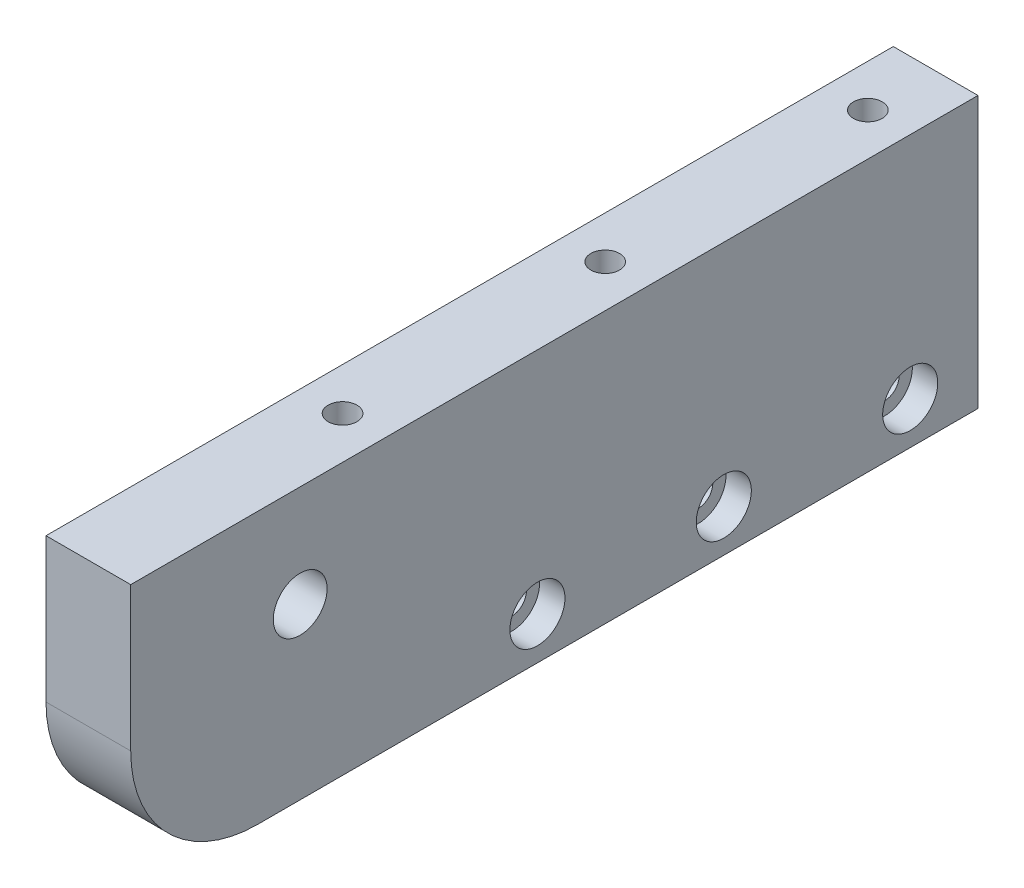
SolidWorks part; units mm, degrees
material "Plain Carbon Steel"
ref_plane "Front Plane" through (0, 0, 0) normal (0, 0, 1) x (1, 0, 0)
ref_plane "Top Plane" through (0, 0, 0) normal (0, 1, 0) x (1, 0, 0)
ref_plane "Right Plane" through (0, 0, 0) normal (1, 0, 0) x (0, 0, -1)
sketch "Sketch1" plane through (0, 0, 0) normal (1, 0, 0) x (0, 0, -1)
  line L1 (-50, -16) -> (50, -16)
  line L2 (-50, -16) -> (-50, 16)
  line L3 (-50, 16) -> (50, 16)
  line L4 (50, -16) -> (50, 16)
  line L5 (-50, -16) -> (50, 16) construction
  line L6 (-50, 16) -> (50, -16) construction
  circle A0 centre (-30, 4) radius 3.175
  point P0 (0, 0)
  dimension "D3" = 6.35
  dimension "D1" = 32
  dimension "D2" = 100
  dimension "D4" = 20
  dimension "D5" = 12
extrude "Boss-Extrude1" add sketch "Sketch1" along normal blind 10 contours L1 L4 L3 L2 A0 | A0 region at (0, -0.04, -0.2999)
fillet "Fillet1" radius 15 1 edges at (5, -16, 50)
hole_wizard "CBORE for M3 SHCS" positions "Sketch4" profile "Sketch5" counterbore size "M3" standard "ANSI Metric"
sketch "Sketch4" plane through (-726.2935, 26, -1323.2827) normal (0, 1, 0) x (1, 0, 0)
  line L3 (621.2935, -1281.2827) -> (621.2935, -1365.2827) construction
  line L5 (731.2935, -1281.2827) -> (731.2935, -1343.2827) construction
  circle A0 centre (731.2935, -1281.2827) radius 2.243
  circle A1 centre (731.2935, -1343.2827) radius 2.2384
  circle A3 centre (621.2935, -1281.2827) radius 2.3325
  circle A4 centre (621.2935, -1365.2827) radius 1.7576
  circle A5 centre (621.2935, -1323.2827) radius 1.8624
  circle A6 centre (731.2935, -1312.2827) radius 2.0271
  point P1 (731.2935, -1281.2827)
  point P8 (731.2935, -1343.2827)
  point P15 (621.2935, -1281.2827)
  point P17 (621.2935, -1365.2827)
  point P19 (621.2935, -1323.2827)
  point P27 (731.2935, -1312.2827)
sketch "Sketch5" plane through (5, 26, -42) normal (1, 0, 0) x (0, 0, 1)
  line L0 (0, 0) -> (0, 24.0215)
  line L1 (0, 24.0215) -> (1.7, 23)
  line L2 (1.7, 23) -> (1.7, 3)
  line L3 (1.7, 3) -> (3.25, 3)
  line L4 (3.25, 3) -> (3.25, 0)
  line L5 (3.25, 0) -> (0, 0)
  line L6 (0, 24.0215) -> (-1.7, 23) construction
  line L7 (0, -6.35) -> (0, 107.95) construction
  dimension "Hole Dia." = 3.4
  dimension "Hole Depth" = 23
  dimension "C'Bore Dia." = 6.5
  dimension "C'Bore Depth" = 3
  dimension "Drill Angle" = 118
hole_wizard "CBORE for M3 SHCS1" positions "Sketch6" profile "Sketch7" counterbore size "M3" standard "ANSI Metric"
sketch "Sketch6" plane through (10, -904.0121, -1323.2827) normal (1, 0, 0) x (0, 0, -1)
  line L0 (-1281.2827, 893.0121) -> (-1325.2827, 893.0121) construction
  point P0 (-1281.2827, 893.0121)
  point P1 (-1325.2827, 893.0121)
  point P9 (-1303.2827, 893.0121)
sketch "Sketch7" plane through (10, -11, -42) normal (0, 1, 0) x (0, 0, -1)
  line L0 (0, 0) -> (0, 24.0215)
  line L1 (0, 24.0215) -> (1.7, 23)
  line L2 (1.7, 23) -> (1.7, 3)
  line L3 (1.7, 3) -> (3.25, 3)
  line L4 (3.25, 3) -> (3.25, 0)
  line L5 (3.25, 0) -> (0, 0)
  line L6 (0, 24.0215) -> (-1.7, 23) construction
  line L7 (0, -6.35) -> (0, 107.95) construction
  dimension "Hole Dia." = 3.4
  dimension "Hole Depth" = 23
  dimension "C'Bore Dia." = 6.5
  dimension "C'Bore Depth" = 3
  dimension "Drill Angle" = 118
